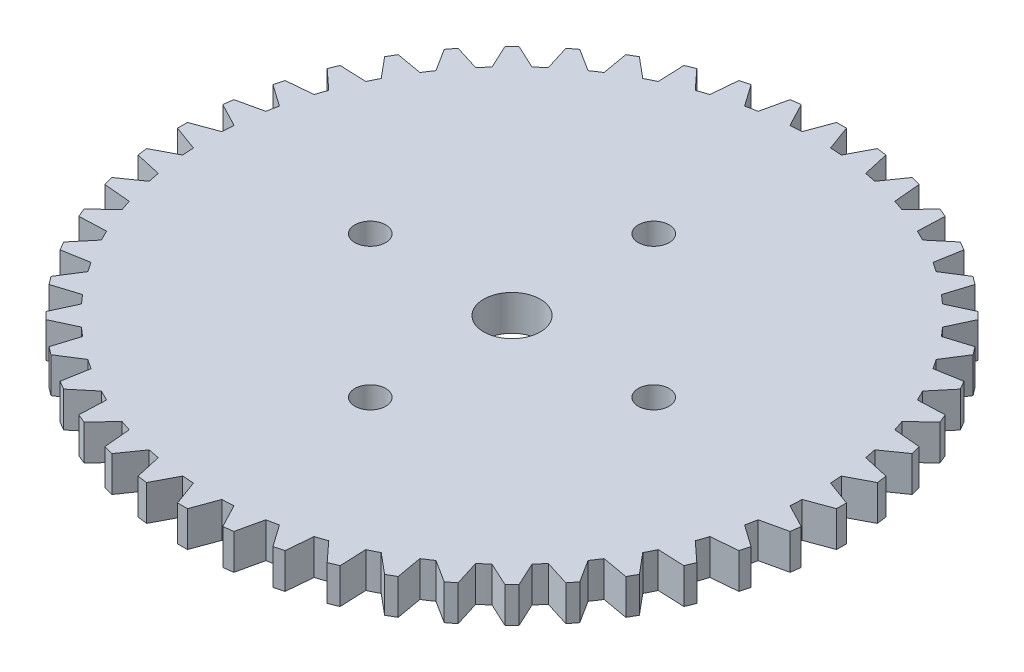
SolidWorks part; units mm, degrees
material "ABS"
ref_plane "Front" through (0, 0, 0) normal (0, 0, 1) x (1, 0, 0)
ref_plane "Top" through (0, 0, 0) normal (0, 1, 0) x (1, 0, 0)
ref_plane "Right" through (0, 0, 0) normal (1, 0, 0) x (0, 0, -1)
sketch "Sketch2" plane through (0, 0, 0) normal (0, 1, 0) x (1, 0, 0)
  circle A0 centre (0, 0) radius 21.5
  circle A1 centre (0, 0) radius 2
  dimension "D1" = 43
  dimension "D2" = 4
extrude "Boss-Extrude1" add sketch "Sketch2" along normal blind 2.5
ref_plane "Plane1" through (0, 0, 0) normal (0, 1, 0) x (1, 0, 0)
sketch "Sketch3" plane through (0, 0, 0) normal (0, 1, 0) x (1, 0, 0)
  line L0 (0, 21.5) -> (0, -21.5) construction
  line L1 (-21.5, 0) -> (21.5, 0) construction
  line L3 (0, 21.5) -> (0, 23.25) construction
  line L4 (-1, 21.4767) -> (-0.35, 23.25)
  line L5 (-0.35, 23.25) -> (0.35, 23.25)
  line L6 (1, 21.4767) -> (0.35, 23.25)
  circle A0 centre (0, 0) radius 21.5 construction
  arc A1 (-21.5, 0) -> (21.5, 0) centre (0, 0) ccw
  arc A2 (1, 21.4767) -> (-1, 21.4767) centre (0, 0) ccw
  dimension "D1" = 2
  dimension "D2" = 0.35
  dimension "D3" = 23.25
extrude "Boss-Extrude2" add sketch "Sketch3" along normal blind 2.5 contours L6 L5 L4 A2
pattern_circular "CirPattern1" count 48 over 360 about axis through (0, 2.5, 0) along (0, 1, 0) of "Boss-Extrude2"
ref_plane "Plane2" through (0, 2.5, 0) normal (0, 1, 0) x (1, 0, 0)
sketch "Sketch5" plane through (0, 2.5, 0) normal (0, 1, 0) x (1, 0, 0)
  line L0 (-34.259, 0) -> (34.259, 0) construction
  line L1 (0, -34.259) -> (0, 34.259) construction
  circle A0 centre (0, 10) radius 1.09
  point P6 (0, 0)
  dimension "D1" = 10
  dimension "D2" = 2.18
extrude "Cut-Extrude2" cut sketch "Sketch5" against normal up to surface (2.5 mm away) up to face at (0, 0, 0)
pattern_circular "CirPattern2" count 4 over 360 about axis through (0, 2.5, 0) along (0, -1, 0) of "Cut-Extrude2"
